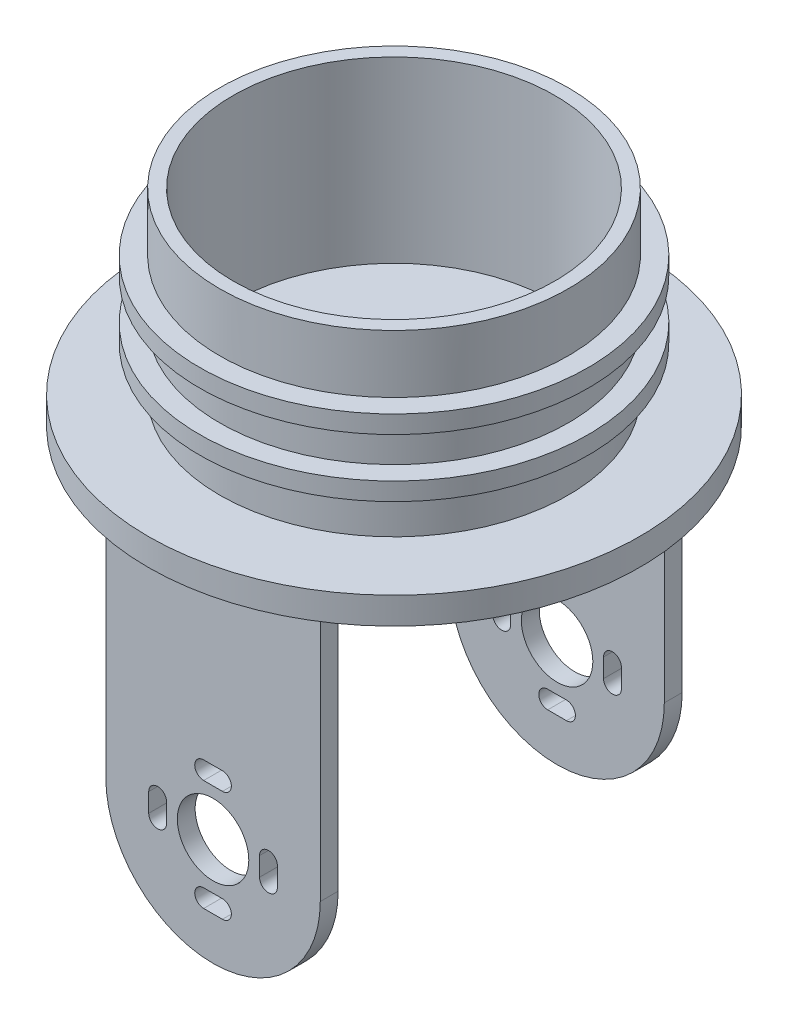
SolidWorks part; units mm, degrees
ref_plane "前基準面" through (0, 0, 0) normal (0, 0, 1) x (1, 0, 0)
ref_plane "上基準面" through (0, 0, 0) normal (0, 1, 0) x (1, 0, 0)
ref_plane "右基準面" through (0, 0, 0) normal (1, 0, 0) x (0, 0, -1)
sketch "草圖1" plane through (0, 0, 0) normal (0, 1, 0) x (1, 0, 0)
  circle A0 centre (0, 0) radius 19.5
  circle A1 centre (0, 0) radius 18
  dimension "D1" = 39
  dimension "D2" = 36
extrude "填料-伸長1" add sketch "草圖1" along normal blind 20
sketch "草圖3" plane through (0, 0, 0) normal (0, -1, 0) x (1, 0, 0)
  circle A0 centre (0, 0) radius 27.5
  dimension "D1" = 55
extrude "填料-伸長2" add sketch "草圖3" along normal blind 3
sketch "草圖4" plane through (0, 0, 0) normal (0, 0, 1) x (1, 0, 0)
  line L0 (0, 20) -> (0, -52.6673) construction
  line L1 (18, 20) -> (-18, 20) construction
  line L2 (-27.5, -3) -> (27.5, -3) construction
  line L3 (-10, -3) -> (10, -3)
  line L4 (-10, -3) -> (-10, -63)
  line L5 (-10, -63) -> (10, -63)
  line L6 (10, -3) -> (10, -63)
  line L8 (-6.5, -28) -> (6.5, -28)
  line L9 (-6.5, -28) -> (-6.5, -53)
  line L10 (-6.5, -53) -> (6.5, -53)
  line L11 (6.5, -28) -> (6.5, -53)
  dimension "D1" = 10
  dimension "D2" = 10
  dimension "D3" = 60
  dimension "D4" = 6.5
  dimension "D5" = 6.5
  dimension "D6" = 25
  dimension "D7" = 25
ref_plane "平面2" through (0, -3, 0) normal (0, -1, 0) x (-1, 0, 0)
ref_plane "平面5" through (0, 0, 0) normal (0, 1, 0) x (1, 0, 0)
ref_plane "平面6" through (0, 7, 0) normal (0, -1, 0) x (-1, 0, 0)
sketch "草圖25" plane through (0, 7, 0) normal (0, -1, 0) x (-1, 0, 0)
  circle A0 centre (0, 0) radius 21.75
  circle A1 centre (0, 0) radius 19.5
  dimension "D1" = 43.5
extrude "填料-伸長12" add sketch "草圖25" along normal blind 2
ref_plane "平面10" through (0, 10.5, 0) normal (0, -1, 0) x (-1, 0, 0)
sketch "草圖26" plane through (0, 10.5, 0) normal (0, -1, 0) x (-1, 0, 0)
  circle A0 centre (0, 0) radius 21.75
  circle A1 centre (0, 0) radius 19.5
extrude "填料-伸長13" add sketch "草圖26" against normal blind 2 from offset 1 offset against normal yes
ref_plane "平面11" through (0, -3, 0) normal (0, -1, 0) x (-1, 0, 0)
sketch "草圖27" plane through (0, -3, 0) normal (0, -1, 0) x (-1, 0, 0)
  line L0 (-27.5, 0) -> (27.5, 0) construction
  line L1 (-12, 20.25) -> (12, 20.25)
  line L2 (-12, 20.25) -> (-12, 18.25)
  line L3 (-12, 18.25) -> (12, 18.25)
  line L4 (12, 20.25) -> (12, 18.25)
  line L5 (-46.0389, 0) -> (46.0389, 0) construction
  line L6 (0, 0) -> (0, -33.56) construction
  line L7 (-12, -18.25) -> (12, -18.25)
  line L8 (12, -20.25) -> (12, -18.25)
  line L9 (-12, -20.25) -> (12, -20.25)
  line L10 (-12, -20.25) -> (-12, -18.25)
  circle A0 centre (0, 0) radius 27.5 construction
  point P13 (-12, 19.25)
  dimension "D1" = 18.25
  dimension "D2" = 24
  dimension "D3" = 12
  dimension "D4" = 2
ref_plane "平面12" through (0, 0, -18.25) normal (0, 0, 1) x (1, 0, 0)
sketch "草圖28" plane through (0, 0, -18.25) normal (0, 0, 1) x (1, 0, 0)
  line L0 (0, -3) -> (0, -48.9232) construction
  line L1 (12, -3) -> (-12, -3) construction
  line L2 (12, -3) -> (-12, -3) construction
  line L3 (-12, -3) -> (12, -3)
  line L4 (-12, -3) -> (-12, -33)
  line L6 (12, -3) -> (12, -33)
  line L7 (-12, -33) -> (12, -33) construction
  line L8 (-1.05, -26.8) -> (1.05, -26.8) construction
  line L9 (-1.05, -25.8) -> (1.05, -25.8)
  line L10 (-1.05, -27.8) -> (1.05, -27.8)
  line L11 (6.2, -31.95) -> (6.2, -34.05) construction
  line L12 (7.2, -31.95) -> (7.2, -34.05)
  line L13 (5.2, -31.95) -> (5.2, -34.05)
  line L14 (-1.05, -39.2) -> (1.05, -39.2) construction
  line L15 (-1.05, -40.2) -> (1.05, -40.2)
  line L16 (-1.05, -38.2) -> (1.05, -38.2)
  line L17 (-6.2, -31.95) -> (-6.2, -34.05) construction
  line L18 (-7.2, -31.95) -> (-7.2, -34.05)
  line L19 (-5.2, -31.95) -> (-5.2, -34.05)
  arc A1 (-12, -33) -> (12, -33) centre (0, -33) ccw
  circle A2 centre (0, -33) radius 4
  arc A3 (-1.05, -25.8) -> (-1.05, -27.8) centre (-1.05, -26.8) ccw
  arc A4 (1.05, -27.8) -> (1.05, -25.8) centre (1.05, -26.8) ccw
  arc A5 (7.2, -31.95) -> (5.2, -31.95) centre (6.2, -31.95) ccw
  arc A6 (5.2, -34.05) -> (7.2, -34.05) centre (6.2, -34.05) ccw
  arc A7 (-1.05, -40.2) -> (-1.05, -38.2) centre (-1.05, -39.2) cw
  arc A8 (1.05, -38.2) -> (1.05, -40.2) centre (1.05, -39.2) cw
  arc A9 (-7.2, -31.95) -> (-5.2, -31.95) centre (-6.2, -31.95) cw
  arc A10 (-5.2, -34.05) -> (-7.2, -34.05) centre (-6.2, -34.05) cw
  point P15 (0, -26.8)
  point P20 (6.2, -33)
  point P32 (0, -39.2)
  point P39 (-6.2, -33)
  dimension "D2" = 0
  dimension "D10" = 8
  dimension "D1" = 30
  dimension "D3" = 0
  dimension "D4" = 6.2
  dimension "D5" = 6.2
  dimension "D6" = 2.1
  dimension "D7" = 2
  dimension "D8" = 2.1
  dimension "D9" = 2
extrude "填料-伸長14" add sketch "草圖28" against normal blind 2
pattern_linear "直線複製排列1" count 2 spacing 38.5 along (0, 0, 1) of "填料-伸長14"
